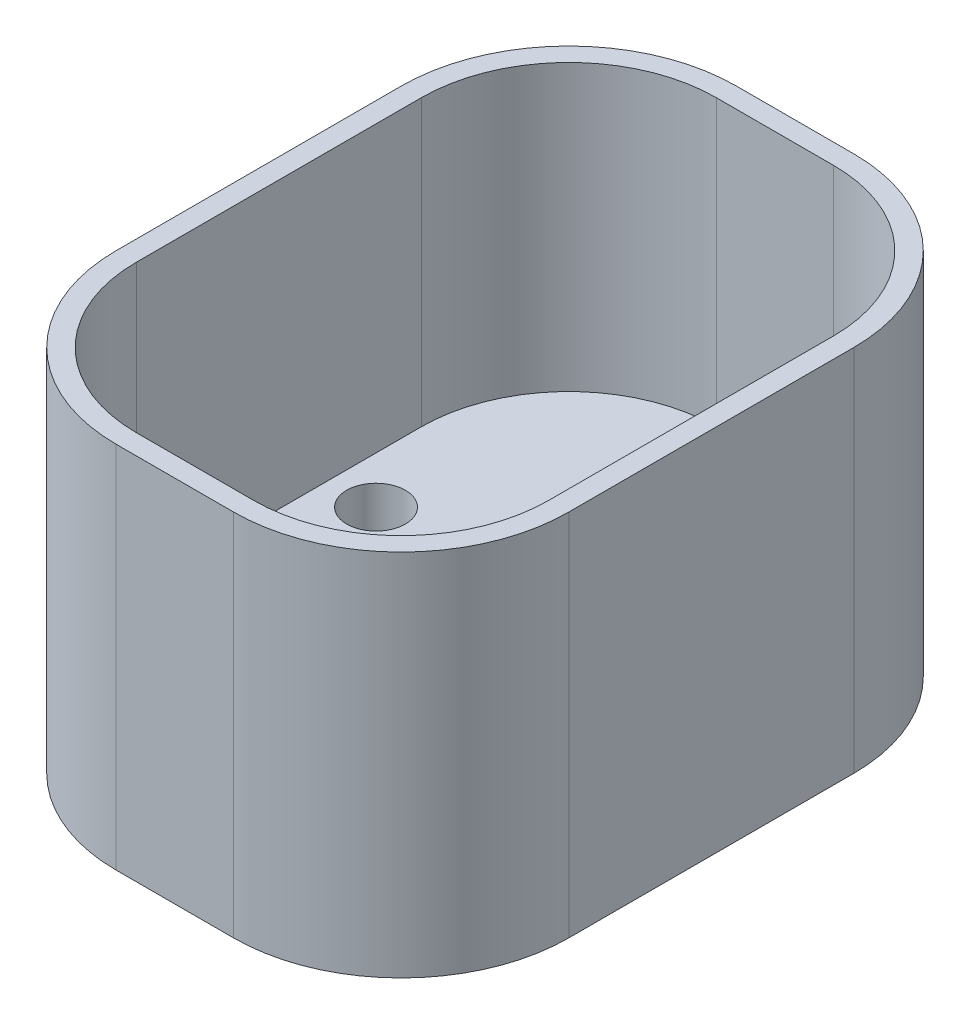
SolidWorks part; units mm, degrees
note: The reader was unsure of these and kept them because the rebuilt part matched: shared geometry of "Sketch1<4>", "Sketch1<5>".
ref_plane "Front Plane" through (0, 0, 0) normal (0, 0, 1) x (1, 0, 0)
ref_plane "Top Plane" through (0, 0, 0) normal (0, 1, 0) x (1, 0, 0)
ref_plane "Right Plane" through (0, 0, 0) normal (1, 0, 0) x (0, 0, -1)
sketch "Sketch1" plane through (0, 0, 0) normal (0, 1, 0) x (1, 0, 0)
  line L0 (0, -55) -> (0, 55) construction
  line L1 (-13.5, 23.5) -> (13.5, 23.5)
  line L2 (-13.5, 23.5) -> (-13.5, -13.5)
  line L3 (-13.5, -13.5) -> (13.5, -13.5)
  line L4 (13.5, 23.5) -> (13.5, -13.5)
  line L5 (5.45, 10.3383) -> (9.5, 12.6765)
  line L6 (-9.5, 12.6765) -> (-13.55, 10.3383)
  line L7 (-13.55, 10.3383) -> (-13.55, 5.6617)
  line L8 (-13.55, 5.6617) -> (-9.5, 3.3235)
  line L9 (-9.5, 3.3235) -> (-5.45, 5.6617)
  line L10 (-5.45, 5.6617) -> (-5.45, 10.3383)
  line L11 (-5.45, 10.3383) -> (-9.5, 12.6765)
  line L12 (5.45, 5.6617) -> (5.45, 10.3383)
  line L13 (9.5, 3.3235) -> (5.45, 5.6617)
  line L14 (13.55, 5.6617) -> (9.5, 3.3235)
  line L15 (13.55, 10.3383) -> (13.55, 5.6617)
  line L16 (9.5, 12.6765) -> (13.55, 10.3383)
  circle A0 centre (0, 0) radius 8.05
  circle A2 centre (0, 13.337) radius 1.5
  circle A3 centre (0, 0) radius 2.8
  circle A4 centre (-9.5, 8) radius 1.75
  circle A6 centre (9.5, 8) radius 1.75
  circle A7 centre (-9.5, 8) radius 4.05 construction
  point P9 (0, -13.5)
  dimension "D1" = 16.1
  dimension "D6" = 3
  dimension "D8" = 5.6
  dimension "D9" = 3.5
  dimension "D11" = 8.1
  dimension "D3" = 27
  dimension "D4" = 37
  dimension "D5" = 13.5
  dimension "D7" = 13.337
  dimension "D2" = 8
  dimension "D10" = 4
extrude "Boss-Extrude1" add sketch "Sketch1" along normal blind 5
extrude "Boss-Extrude3" add sketch "Sketch1<4>" along normal blind 4.95 contours A2
sketch "Sketch1<4>" plane through (0, 0, 0) normal (0, 1, 0) x (1, 0, 0) same geometry as "Sketch1"
extrude "Boss-Extrude4" add sketch "Sketch1<5>" along normal blind 2 contours A0 A3 | L10 A0 L9 | L13 A0 L12
sketch "Sketch1<5>" plane through (0, 0, 0) normal (0, 1, 0) x (1, 0, 0) same geometry as "Sketch1"
fillet "Fillet1" radius 10 4 edges at (13.5, 2.5, -23.5) (13.5, 2.5, 13.5) (-13.5, 2.5, 13.5) (-13.5, 2.5, -23.5)
sketch "Sketch2" plane through (0, 5, 0) normal (0, 1, 0) x (1, 0, 0)
  line L4 (-12.3, 13.5) -> (-12.3, -3.5)
  line L5 (-3.5, -12.3) -> (3.5, -12.3)
  line L6 (12.3, -3.5) -> (12.3, 13.5)
  line L7 (3.5, 22.3) -> (-3.5, 22.3)
  line L12 (13.5, -3.5) -> (13.5, 13.5)
  line L13 (3.5, 23.5) -> (-3.5, 23.5)
  line L14 (-13.5, 13.5) -> (-13.5, -3.5)
  line L15 (-3.5, -13.5) -> (3.5, -13.5)
  line L17 (13.5, -3.5) -> (13.5, 13.5)
  line L18 (3.5, 23.5) -> (-3.5, 23.5)
  line L19 (-13.5, 13.5) -> (-13.5, -3.5)
  line L20 (-3.5, -13.5) -> (3.5, -13.5)
  arc A4 (-12.3, -3.5) -> (-3.5, -12.3) centre (-3.5, -3.5) ccw
  arc A5 (3.5, -12.3) -> (12.3, -3.5) centre (3.5, -3.5) ccw
  arc A6 (12.3, 13.5) -> (3.5, 22.3) centre (3.5, 13.5) ccw
  arc A12 (-3.5, 22.3) -> (-12.3, 13.5) centre (-3.5, 13.5) ccw
  arc A13 (13.5, 13.5) -> (3.5, 23.5) centre (3.5, 13.5) ccw
  arc A14 (-3.5, 23.5) -> (-13.5, 13.5) centre (-3.5, 13.5) ccw
  arc A15 (-13.5, -3.5) -> (-3.5, -13.5) centre (-3.5, -3.5) ccw
  arc A16 (3.5, -13.5) -> (13.5, -3.5) centre (3.5, -3.5) ccw
  arc A17 (13.5, 13.5) -> (3.5, 23.5) centre (3.5, 13.5) ccw
  arc A19 (-3.5, 23.5) -> (-13.5, 13.5) centre (-3.5, 13.5) ccw
  arc A21 (-13.5, -3.5) -> (-3.5, -13.5) centre (-3.5, -3.5) ccw
  arc A22 (3.5, -13.5) -> (13.5, -3.5) centre (3.5, -3.5) ccw
  dimension "D1" = 0
  dimension "D2" = 1.2
extrude "Boss-Extrude5" add sketch "Sketch2" along normal blind 17
equation "\"D5@Sketch1\"=\"D3@Sketch1\"/2"
